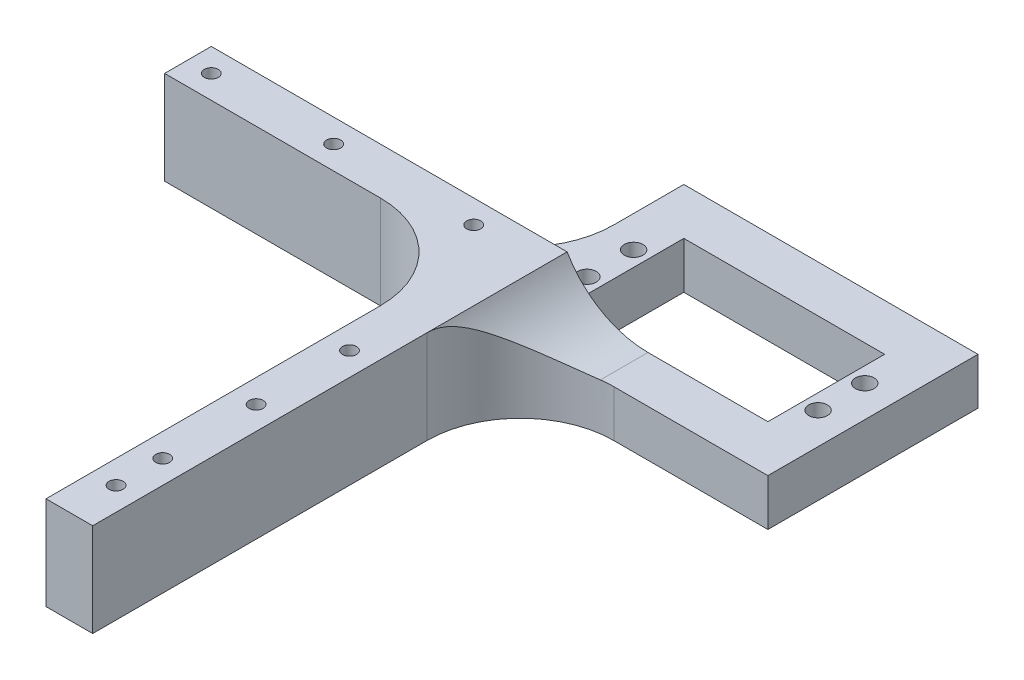
SolidWorks part; units mm, degrees
ref_plane "Front" through (0, 0, 0) normal (0, 0, 1) x (1, 0, 0)
ref_plane "Top" through (0, 0, 0) normal (0, 1, 0) x (1, 0, 0)
ref_plane "Right" through (0, 0, 0) normal (1, 0, 0) x (0, 0, -1)
sketch "Sketch1" plane through (0, 0, 0) normal (0, 1, 0) x (1, 0, 0)
  line L0 (0, 5) -> (0, -5)
  line L1 (-21.5, 12.5) -> (21.5, 12.5)
  line L2 (-21.5, 12.5) -> (-21.5, -12.5)
  line L3 (-21.5, -12.5) -> (21.5, -12.5)
  line L4 (21.5, 12.5) -> (21.5, -12.5)
  line L5 (-21.5, 12.5) -> (21.5, -12.5) construction
  line L6 (-21.5, -12.5) -> (21.5, 12.5) construction
  line L7 (-31.5, 22.5) -> (31.5, 22.5)
  line L8 (-31.5, 22.5) -> (-31.5, -22.5)
  line L9 (-31.5, -22.5) -> (31.5, -22.5)
  line L10 (31.5, 22.5) -> (31.5, -22.5)
  line L11 (-31.5, 22.5) -> (31.5, -22.5) construction
  line L12 (-31.5, -22.5) -> (31.5, 22.5) construction
  line L13 (-24.75, 5) -> (24.75, 5)
  line L14 (-24.75, -5) -> (24.75, -5)
  circle A0 centre (-24.75, 5) radius 2
  circle A1 centre (-24.75, -5) radius 2
  circle A2 centre (24.75, 5) radius 2
  circle A3 centre (24.75, -5) radius 2
  point P0 (0, 0)
  point P6 (0, 0)
  point P14 (0, 0)
  point P17 (0, 5)
  point P20 (0, -5)
  dimension "D1" = 43
  dimension "D2" = 25
  dimension "D3" = 10
  dimension "D4" = 10
  dimension "D5" = 10
  dimension "D6" = 49.5
extrude "Boss-Extrude1" add sketch "Sketch1" along normal blind 10 contours L10 L7 L8 L9 A3 L4 L3 L2 A1 A0 L1 A2 region at (0, 0, -21.7258)
sketch "Sketch2" plane through (-31.5, 0, 0) normal (-1, 0, 0) x (0, 0, 1)
  line L0 (-22.5, 0) -> (22.5, 0) construction
  line L1 (22.5, 10) -> (12.5, 10)
  line L3 (22.5, 0) -> (12.5, 0)
  line L5 (12.5, 0) -> (12.5, 20)
  line L6 (12.5, 20) -> (22.5, 20)
  line L7 (22.5, 10) -> (22.5, 0) construction
  line L8 (22.5, 20) -> (22.5, 0)
  line M3 (-22.5, 0) -> (22.5, 0)
  line M4 (22.5, 0) -> (22.5, 10)
  line M5 (22.5, 10) -> (-22.5, 10)
  dimension "D1" = 10
  dimension "D2" = 10
  dimension "D3" = 20
extrude "Boss-Extrude2" add sketch "Sketch2" along normal blind 76.2 contours L6 L5 M3 M4 | L8 L6 L5 M5 region at (-31.5, 5, 17.5) region at (-31.5, 15, 17.5)
sketch "Sketch3" plane through (0, 0, 22.5) normal (0, 0, 1) x (1, 0, 0)
  line L0 (-107.7, 0) -> (31.5, 0) construction
  line L1 (-21.5, 10) -> (-31.5, 10)
  line L2 (-21.5, 10) -> (-21.5, 0)
  line L3 (-21.5, 0) -> (-31.5, 0)
  line L4 (-31.5, 10) -> (-31.5, 0)
  line L5 (-107.7, 0) -> (-107.7, 20) construction
  dimension "D1" = 10
  dimension "D2" = 76.2
  dimension "D3" = 10
extrude "Boss-Extrude3" add sketch "Sketch3" along normal blind 91.6
sketch "Sketch5" plane through (0, 10, 0) normal (0, 1, 0) x (1, 0, 0)
  line L0 (-31.5, -12.5) -> (-21.5, -12.5)
  line L1 (-21.5, -12.5) -> (-21.5, -114.1)
  line L2 (-21.5, -114.1) -> (-31.5, -114.1)
  line L3 (-31.5, -114.1) -> (-31.5, -12.5)
extrude "Boss-Extrude4" add sketch "Sketch5" along normal blind 10
sketch "Sketch4" plane through (0, 10, 0) normal (0, 1, 0) x (1, 0, 0)
  line L0 (-107.7, -17.5) -> (-66.5, -17.5)
  line L1 (-107.7, -22.5) -> (-107.7, -12.5) construction
  line L2 (-66.5, -17.5) -> (-36.5, -17.5)
  circle A0 centre (-92.7, -17.5) radius 1.5
  circle A1 centre (-66.5, -17.5) radius 1.5
  circle A2 centre (-36.5, -17.5) radius 1.5
  dimension "D1" = 41.2
  dimension "D2" = 30
  dimension "D3" = 15
extrude "Cut-Extrude1" cut sketch "Sketch4" against normal through all and the other way through all contours L0 A0 | L0 A0 | A1 | A2 region at (-92.7, 10, 16.8634) region at (-92.7, 10, 18.1366)
fillet "Fillet5" radius 20 2 edges at (-31.5, 5, 12.5) (-31.5, 10, 22.5)
fillet "Fillet7" radius 20 1 edges at (-21.5, 10, 17.5)
fillet "Fillet8" radius 3 1 edges at (-36.5, 10, 12.5)
fillet "Fillet9" radius 20 1 edges at (-21.5, 10, 22.5)
sketch "Sketch6" plane through (-107.7, 0, 0) normal (-1, 0, 0) x (0, 0, 1)
  line L1 (12.5, 0) -> (22.5, 0)
  line L2 (12.5, 0) -> (12.5, 20)
  line L3 (12.5, 20) -> (22.5, 20)
  line L4 (22.5, 0) -> (22.5, 20)
extrude "Cut-Extrude2" cut sketch "Sketch6" against normal blind 10
sketch "Sketch7" plane through (0, 0, 0) normal (0, -1, 0) x (-1, 0, 0)
  line L0 (26.5, -114.1) -> (26.5, -94.1)
  line L1 (31.5, -114.1) -> (21.5, -114.1) construction
  line L2 (26.5, -94.1) -> (26.5, -54.1)
  circle A0 centre (26.5, -54.1) radius 1.5
  circle A1 centre (26.5, -94.1) radius 1.5
  circle A2 centre (26.5, -74.1) radius 1.5
  circle A3 centre (26.5, -104.1) radius 1.5
  dimension "D1" = 20
  dimension "D2" = 40
extrude "Cut-Extrude3" cut sketch "Sketch7" against normal through all contours A1 | A0 | A3 | A2
